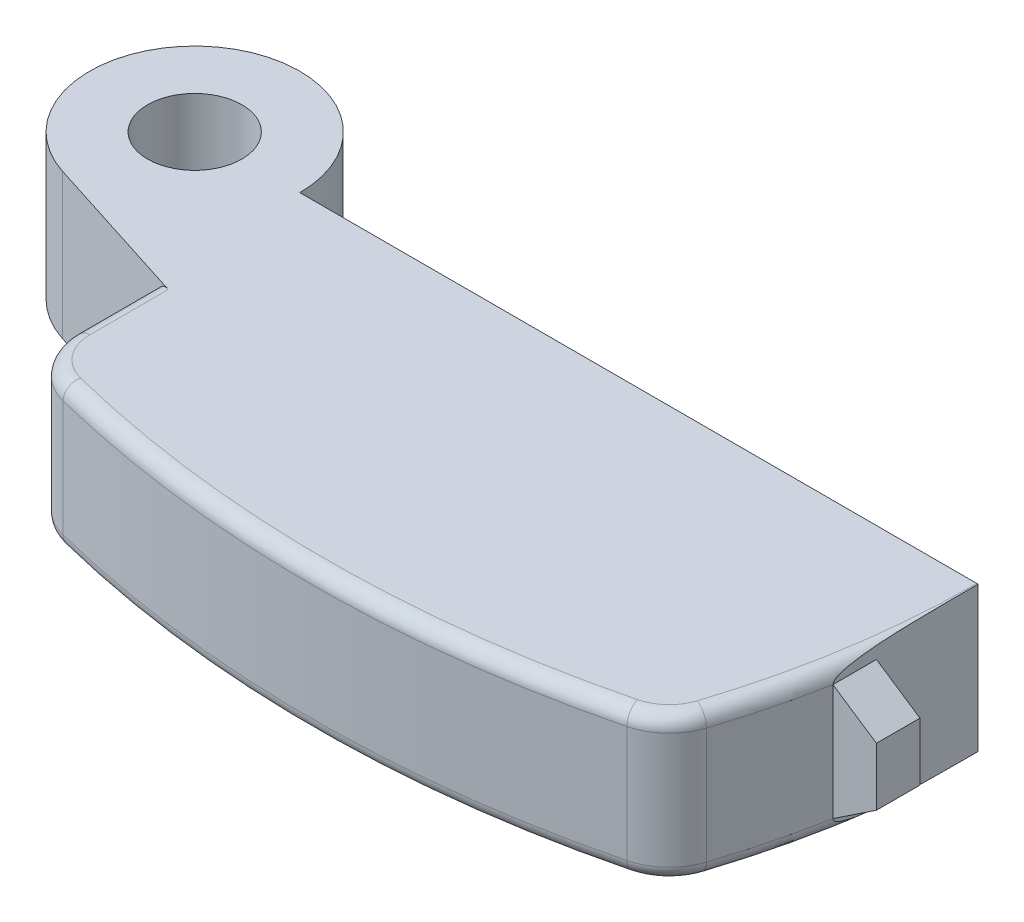
SolidWorks part; units mm, degrees
ref_plane "Front Plane" through (0, 0, 0) normal (0, 0, 1) x (1, 0, 0)
ref_plane "Top Plane" through (0, 0, 0) normal (0, 1, 0) x (1, 0, 0)
ref_plane "Right Plane" through (0, 0, 0) normal (1, 0, 0) x (0, 0, -1)
sketch "Sketch1" plane through (0, 0, 0) normal (0, 1, 0) x (1, 0, 0)
  line L0 (3.625, 0) -> (27, 0)
  line L2 (3.75, -7.8614) -> (3.75, -5)
  line L3 (-1.1009, -3.4538) -> (3.75, -5)
  line L4 (5.3249, -11) -> (19.1895, -11) construction
  line L5 (5.2641, -9.8015) -> (24.7008, -9.8015) construction
  line L7 (27, 0) -> (27, -5)
  arc A1 (26.1172, -8.479) -> (24.7008, -9.8015) centre (24.2149, -7.8614) cw
  circle A2 centre (0, 0) radius 1.625
  arc A3 (3.625, 0) -> (-1.1009, -3.4538) centre (0, 0) ccw
  arc A5 (3.75, -7.8614) -> (5.2641, -9.8015) centre (5.75, -7.8614) ccw
  arc A6 (5.2641, -9.8015) -> (24.7008, -9.8015) centre (14.9825, 29) ccw
  arc A7 (27, -5) -> (26.1172, -8.479) centre (0, 0) cw
  point P9 (25.9504, -3.1927)
  point P13 (27, -4.7764)
  point P18 (24.4878, -9.8287)
  point P19 (25.2975, -7.448)
  point P20 (0, 0)
  point P21 (0, 0)
  point P23 (26.2104, -8.4644)
  point P24 (24.4725, -9.8306)
  point P25 (0, 0)
  point P26 (1.4446, -3.3247)
  point P27 (-0.792, -3.5374)
  dimension "D1" = 27
  dimension "D3" = 2
  dimension "D2" = 3.25
  dimension "D4" = 2
  dimension "D6" = 40
  dimension "D5" = 11
  dimension "D7" = 3.75
  dimension "D8" = 5
extrude "Boss-Extrude1" add sketch "Sketch1" against normal mid plane 5
shell "Shell1" [suppressed] thickness 1.5
ref_plane "Plane1" through (0, 0, 5) normal (0, 0, 1) x (1, 0, 0)
sketch "Sketch3" plane through (0, 0, 5) normal (0, 0, -1) x (-1, 0, 0)
  line L0 (-27, -2.5) -> (-27, -2) construction
  line L6 (-27, -2) -> (-28.5, -1)
  line L7 (-28.5, -1) -> (-28.5, 1)
  line L8 (-28.5, 1) -> (-27, 2)
  line L9 (-27, 2) -> (-27, 2.5) construction
  line L11 (-27, 2) -> (-27, -2)
  line L12 (-27, -2.5) -> (-27, 2.5) construction
  point P0 (-27, -2.239)
  dimension "D1" = 1.5
  dimension "D2" = 2
  dimension "D3" = 4
extrude "Boss-Extrude2" add sketch "Sketch3" along normal blind 1.5 contours L6 L7 L8 L11
fillet "Fillet1" radius 0.5 10 edges at (3.75, 2.5, 6.4307) (4.1733, 2.5, 9.0919) (26.6155, 2.5, 6.7539) (25.5799, 2.5, 9.3232) (3.75, -2.5, 6.4307) (4.1733, -2.5, 9.0919) (26.6155, -2.5, 6.7539) (25.5799, -2.5, 9.3232) (14.9825, 2.5, 11) (14.9825, -2.5, 11)
